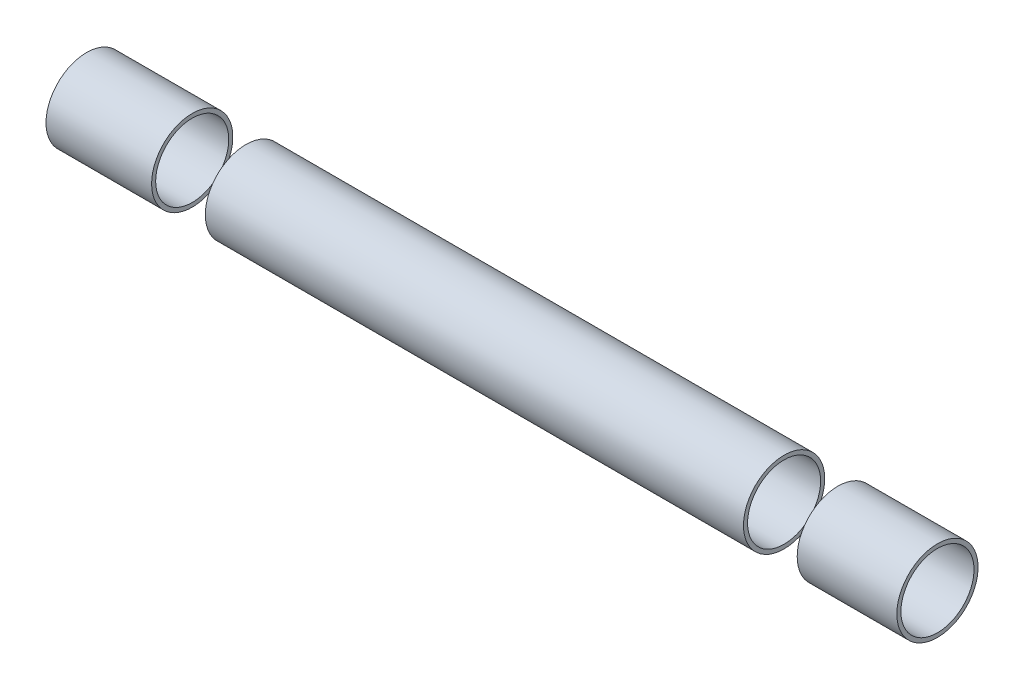
SolidWorks part; units mm, degrees
material "PC High Viscosity"
ref_plane "Front Plane" through (0, 0, 0) normal (0, 0, 1) x (1, 0, 0)
ref_plane "Top Plane" through (0, 0, 0) normal (0, 1, 0) x (1, 0, 0)
ref_plane "Right Plane" through (0, 0, 0) normal (1, 0, 0) x (0, 0, -1)
sketch "Sketch1" plane through (0, 0, 0) normal (1, 0, 0) x (0, 0, -1)
  circle A0 centre (0, 0) radius 15.875
  dimension "D1" = 31.75
extrude "Extrude-Thin1" add sketch "Sketch1" along normal mid plane 334.899 thin thin type one direction reverse wall 1.5875
sketch "Sketch2" plane through (0, 0, 0) normal (0, 0, 1) x (1, 0, 0)
  line L0 (-167.4495, -15.875) -> (167.4495, -15.875) construction
  line L1 (105.1745, -15.875) -> (126.1745, -15.875)
  line L2 (105.1745, -15.875) -> (105.1745, 15.875)
  line L3 (105.1745, 15.875) -> (126.1745, 15.875)
  line L4 (126.1745, -15.875) -> (126.1745, 15.875)
  line L5 (167.4495, 15.875) -> (-167.4495, 15.875) construction
  line L6 (167.4495, -15.875) -> (167.4495, 15.875) construction
  line L7 (0, 0) -> (0, 11.1276) construction
  line L8 (-126.1745, -15.875) -> (-126.1745, 15.875)
  line L9 (-105.1745, 15.875) -> (-126.1745, 15.875)
  line L10 (-105.1745, -15.875) -> (-105.1745, 15.875)
  line L11 (-105.1745, -15.875) -> (-126.1745, -15.875)
  line L13 (167.4495, -15.875) -> (165.1254, -15.875)
  line L14 (167.4495, -15.875) -> (167.4495, 15.875)
  line L15 (167.4495, 15.875) -> (165.1254, 15.875)
  line L16 (165.1254, -15.875) -> (165.1254, 15.875)
  dimension "D1" = 41.275
  dimension "D2" = 21
  dimension "D3" = 2.3241
extrude "Cut-Extrude1" cut sketch "Sketch2" against normal through all both and the other way through all
equation "\"D2@Sketch2\"=21mm"
